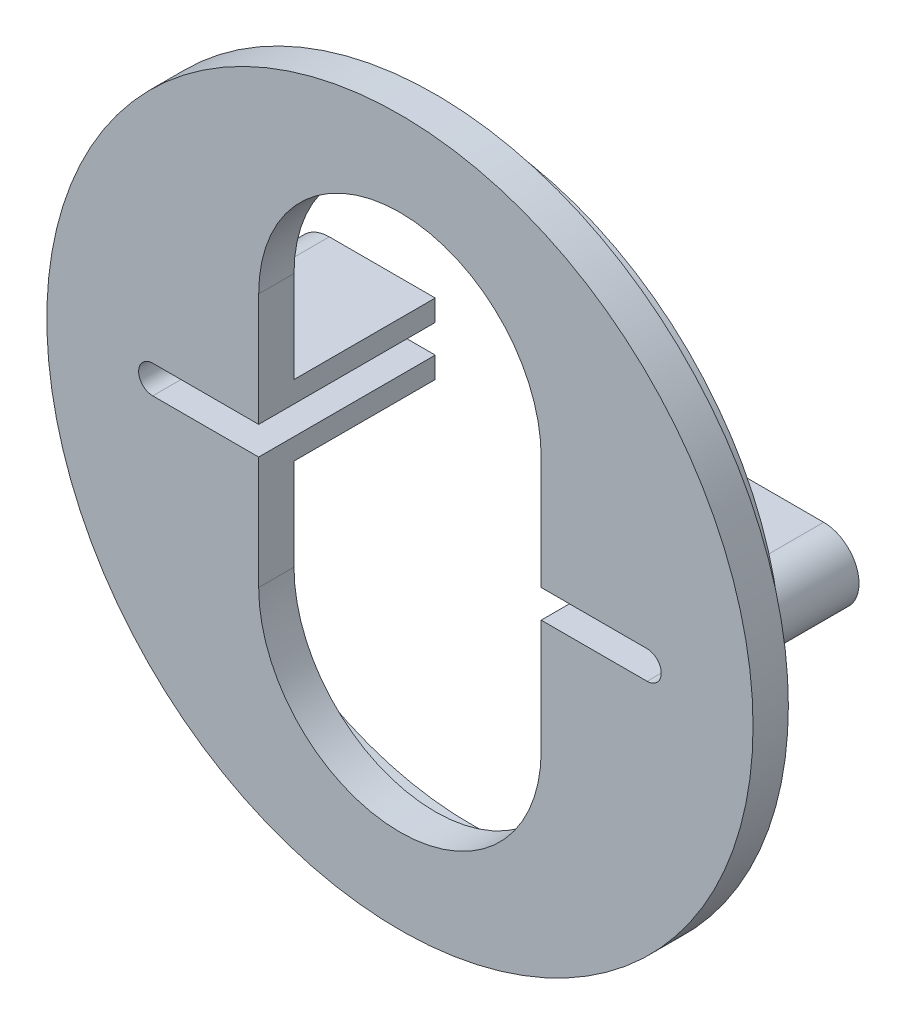
SolidWorks part; units mm, degrees
ref_plane "Plano frontal" through (0, 0, 0) normal (0, 0, 1) x (1, 0, 0)
ref_plane "Plano superior" through (0, 0, 0) normal (0, 1, 0) x (1, 0, 0)
ref_plane "Plano direito" through (0, 0, 0) normal (1, 0, 0) x (0, 0, -1)
sketch "Esboço1" plane through (0, 0, 0) normal (0, 0, 1) x (1, 0, 0)
  line L0 (0, 0) -> (0, 38)
  line L1 (0, 0) -> (0, -38)
  line L2 (0, 38) -> (0, 27.8356)
  line L3 (0, 38) -> (0, 18)
  line L4 (0, 0) -> (80, 0)
  line L5 (-20, 18) -> (-20, 2)
  line L6 (0, 0) -> (-35, 0)
  line L7 (20, 18) -> (20, -18)
  line L8 (-20, 2) -> (-35, 2)
  line L9 (-20, -2) -> (-35, -2)
  line L10 (-20, 5) -> (-35, 5)
  line L11 (-20, -5) -> (-35, -5)
  line L12 (-20, -2) -> (-20, -18)
  line L13 (0, 5) -> (-35, 5) construction
  line L14 (0, 2) -> (-35, 2) construction
  line L15 (0, -2) -> (-35, -2) construction
  line L16 (0, -5) -> (-35, -5) construction
  line L17 (20, -5) -> (35, -5)
  line L18 (20, -2) -> (35, -2)
  line L19 (20, 2) -> (35, 2)
  line L20 (20, 5) -> (35, 5)
  circle A0 centre (0, 0) radius 50
  circle A1 centre (0, 0) radius 42
  arc A2 (20, 18) -> (-20, 18) centre (0, 18) ccw
  arc A3 (20, -18) -> (-20, -18) centre (0, -18) cw
  arc A4 (-35, 2) -> (-35, -2) centre (-35, 0) ccw
  arc A5 (-35, 5) -> (-35, -5) centre (-35, 0) ccw
  arc A6 (35, 5) -> (35, -5) centre (35, 0) cw
  arc A7 (35, 2) -> (35, -2) centre (35, 0) cw
  circle A8 centre (0, 0) radius 44
extrude "Ressalto-extrusão1" add sketch "Esboço1" along normal blind 5 contours A8 A0 | A8 A1 | A6 L17 L7 A3 L12 L11 A5 L10 L5 A2 L20 A1 | L19 A7 L4 A6 L20 L7 | L4 A7 L18 L7 L17 A6 | L10 A5 L11 L12 L9 A4 L8 L5 region at (-40.8121, 0, 0) region at (-42.7555, 0, 0) region at (-48.5858, 0, 0) region at (30.1458, 3.1955, 0) region at (30.1458, -3.1955, 0) region at (-27.5, -4.7764, 0)
extrude "Ressalto-extrusão2" add sketch "Esboço1<3>" against normal blind 20 contours L19 A7 L4 A6 L20 L7 | L4 A7 L18 L7 L17 A6 | L10 A5 L11 L12 L9 A4 L8 L5 region at (30.1458, 3.1955, 0) region at (30.1458, -3.1955, 0) region at (-27.5, -4.7764, 0)
sketch "Esboço1<3>" plane through (0, 0, 0) normal (0, 0, 1) x (1, 0, 0) same geometry as "Esboço1"
extrude "Ressalto-extrusão3" add sketch "Esboço1<4>" against normal blind 5 contours A8 A1 region at (-42.7555, 0, 0)
sketch "Esboço1<4>" plane through (0, 0, 0) normal (0, 0, 1) x (1, 0, 0) same geometry as "Esboço1"
